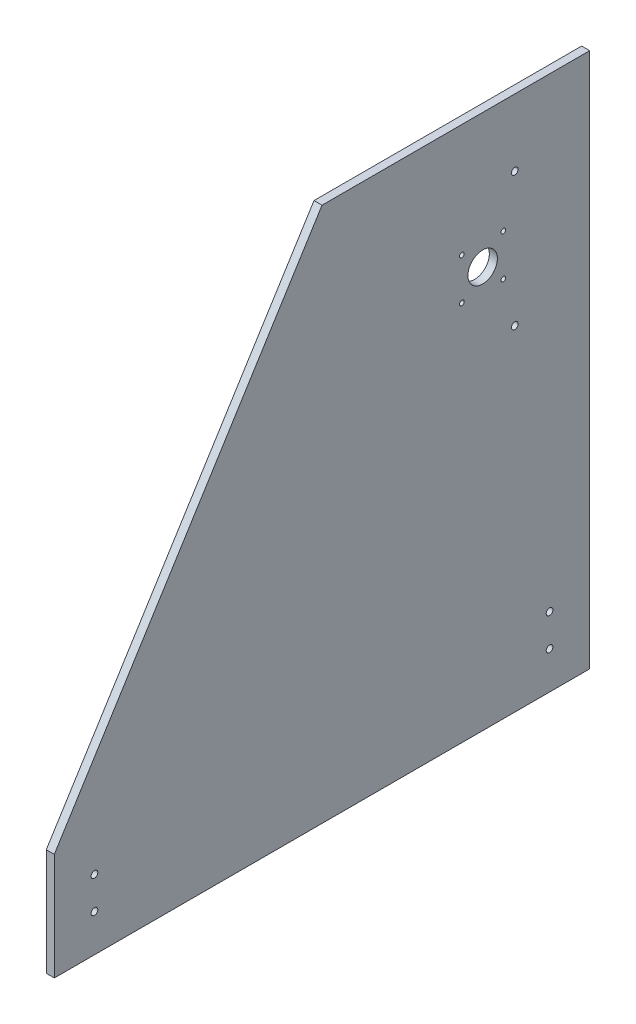
SolidWorks part; units mm, degrees
material "Wrought Stainless Steel"
ref_plane "Front Plane" through (0, 0, 0) normal (0, 0, 1) x (1, 0, 0)
ref_plane "Top Plane" through (0, 0, 0) normal (0, 1, 0) x (1, 0, 0)
ref_plane "Right Plane" through (0, 0, 0) normal (1, 0, 0) x (0, 0, -1)
sketch "Sketch1" plane through (0, 0, 0) normal (1, 0, 0) x (0, 0, -1)
  line L0 (0, -2343.7616) -> (0, 114844.3172) construction
  line L1 (-2343.7616, 0) -> (114844.3172, 0) construction
  line L2 (0, 80) -> (400, 80) construction
  line L3 (0, 0) -> (400, 0)
  line L5 (200, 400) -> (400, 400)
  line L6 (400, 0) -> (400, 400)
  line L7 (0, 80) -> (200, 400)
  line L8 (0, 80) -> (0, 0)
  line L9 (-1000, 40) -> (49000, 40) construction
  line L10 (200, -1000) -> (200, 49000) construction
  line L11 (344, -1000) -> (344, 49000) construction
  line L12 (320, -1008.4066) -> (320, 48991.5934) construction
  line L13 (332.2689, 300) -> (307.7311, 300) construction
  circle A0 centre (30, 52) radius 2.5
  circle A2 centre (30, 28) radius 2.5
  circle A3 centre (370, 28) radius 2.5
  circle A4 centre (370, 52) radius 2.5
  circle A5 centre (344, 350) radius 2.5
  circle A6 centre (344, 250) radius 2.5
  circle A7 centre (320, 300) radius 11
  circle A8 centre (335.5, 315.5) radius 1.75
  circle A9 centre (304.5, 315.5) radius 1.75
  circle A10 centre (304.5, 284.5) radius 1.75
  circle A11 centre (335.5, 284.5) radius 1.75
  point P14 (0, 40)
  point P21 (200, 0)
  point P38 (320, 300)
  dimension "D7" = 5
  dimension "D9" = 5
  dimension "D14" = 22
  dimension "D16" = 15.5
  dimension "D17" = 3.5
  dimension "D1" = 400
  dimension "D2" = 400
  dimension "D3" = 80
  dimension "D4" = 200
  dimension "D5" = 30
  dimension "D6" = 56
  dimension "D8" = 12
  dimension "D10" = 50
  dimension "D11" = 100
  dimension "D12" = 80
  dimension "D13" = 50
  dimension "D15" = 15.5
extrude "Boss-Extrude1" add sketch "Sketch1" along normal blind 6
